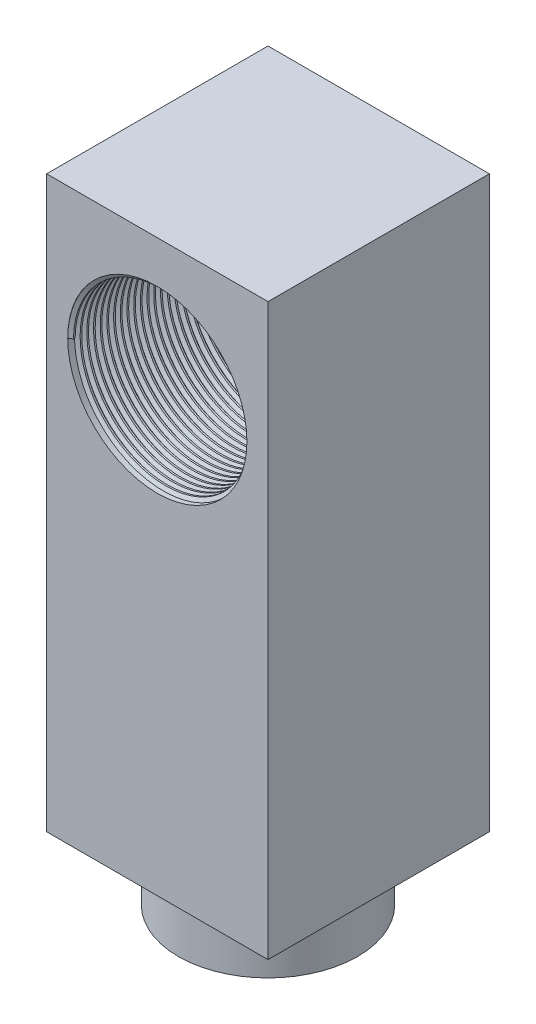
SolidWorks part; units mm, degrees
ref_plane "Front Plane" through (0, 0, 0) normal (0, 0, 1) x (1, 0, 0)
ref_plane "Top Plane" through (0, 0, 0) normal (0, 1, 0) x (1, 0, 0)
ref_plane "Right Plane" through (0, 0, 0) normal (1, 0, 0) x (0, 0, -1)
sketch "Sketch1" plane through (0, 0, 0) normal (0, 1, 0) x (1, 0, 0)
  line L1 (-5.25, -5.25) -> (5.25, -5.25)
  line L2 (-5.25, -5.25) -> (-5.25, 5.25)
  line L3 (-5.25, 5.25) -> (5.25, 5.25)
  line L4 (5.25, -5.25) -> (5.25, 5.25)
  line L5 (-5.25, -5.25) -> (5.25, 5.25) construction
  line L6 (-5.25, 5.25) -> (5.25, -5.25) construction
  point P0 (0, 0)
  dimension "D1" = 10.5
  dimension "D2" = 10.5
extrude "Boss-Extrude3" add sketch "Sketch1" along normal blind 27.03
sketch "Sketch13" plane through (0, 0, 0) normal (0, -1, 0) x (1, 0, 0)
  circle A0 centre (0, 0) radius 4.25
extrude "Boss-Extrude4" add sketch "Sketch13" along normal blind 3
sketch "Sketch14" plane through (0, 0, 5.25) normal (0, 0, 1) x (1, 0, 0)
  circle A0 centre (0, 20.78) radius 4.25
extrude "Cut-Extrude3" cut sketch "Sketch14" against normal blind 15
thread "Thread5" pitch 0.3175 method extrude profile "Thread Profile6" start angle 0, offset 0, length 10.25, pitch 0.3175, diameter 8.5
ref_plane "Plane6" through (-4.25, 20.78, 5.25) normal (0, -1, 0) x (-1, 0, 0)
sketch "Thread Profile6" plane through (-4.25, 20.78, 5.25) normal (0, -1, 0) x (-1, 0, 0)
  line L0 (0, 0) -> (0, 0.3175) construction
  line L11 (0, 0) -> (0, 0.2778)
  line L12 (0, 0.2778) -> (-0.1719, 0.1786)
  line L13 (-0.1719, 0.1786) -> (-0.1719, 0.0992)
  line L15 (-0.1719, 0.0992) -> (0, 0)
  line L17 (-0.1719, 0.1389) -> (0, 0.1389) construction
  point P2 (0, 0)
  dimension "Pitch" = 0.3175
  dimension "Profile_Angle" = 60
  dimension "Profile_Land" = 0.0794
  dimension "Profile_Height" = 0.1719
